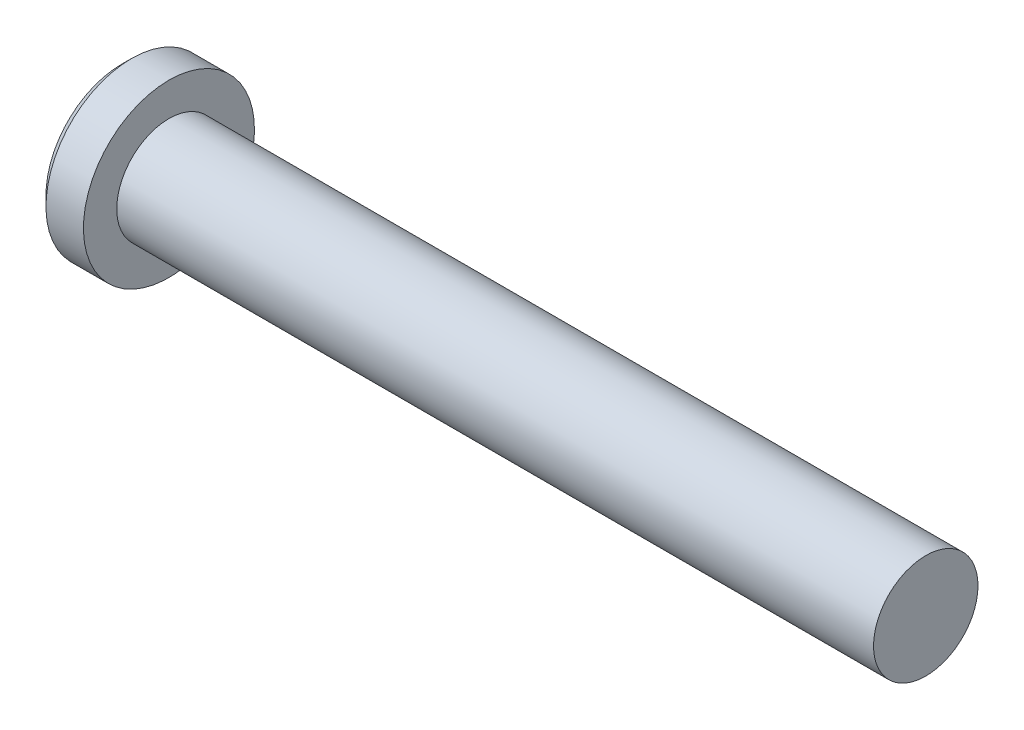
SolidWorks part; units mm, degrees
ref_plane "Front Plane" through (0, 0, 0) normal (0, 0, 1) x (1, 0, 0)
ref_plane "Top Plane" through (0, 0, 0) normal (0, 1, 0) x (1, 0, 0)
ref_plane "Right Plane" through (0, 0, 0) normal (1, 0, 0) x (0, 0, -1)
sketch "Sketch1" plane through (0, 0, 0) normal (0, 0, 1) x (1, 0, 0)
  line L0 (12.7, 0) -> (-12.7, 0) construction
  line L1 (12.7, 1.7526) -> (12.7, -1.7526) construction
  line L2 (-12.7, 2.8702) -> (-12.7, -2.8702) construction
  line L3 (-12.7, 2.8702) -> (-13.9573, 2.8702) construction
  line L4 (-13.9573, 2.8702) -> (-14.2875, 2.54) construction
  line L5 (-14.2875, 2.54) -> (-14.2875, -2.54) construction
  line L6 (-14.2875, -2.54) -> (-13.9573, -2.8702) construction
  line L7 (-13.9573, -2.8702) -> (-12.7, -2.8702) construction
  point P7 (-13.0175, 0)
  point P12 (9.525, -1.7526)
  dimension "D1" = 45
  dimension "Dec." = 3.5052
  dimension "Length" = 25.4
  dimension "Head Dia" = 5.7404
  dimension "Head Height" = 1.5875
  dimension "Hex Depth" = 1.27
  dimension "Chamfer" = 0.3302
  dimension "D2" = 3.175
ref_plane "Plane1" through (12.7, 0, 0) normal (1, 0, 0) x (0, 0, -1)
ref_plane "Plane2" through (-14.2875, 0, 0) normal (1, 0, 0) x (0, 0, -1)
sketch "Sketch2" plane through (12.7, 0, 0) normal (1, 0, 0) x (0, 0, -1)
  circle A0 centre (0, 0) radius 1.7526
extrude "Boss-Extrude1" add sketch "Sketch2" against normal up to vertex (25.4 mm away) up to point (-12.7, 0, 0)
sketch "Sketch3" plane through (12.7, 0, 0) normal (1, 0, 0) x (0, 0, -1)
  circle A0 centre (0, 0) radius 1.7526 construction
  circle A1 centre (0, 0) radius 1.7526
curve "Helix/Spiral1" pitch 0.7937 height 26.1937 turns 33 parameters "Pitch"=0.7937
chamfer "Chamfer1" [suppressed] distance 0.5953 angle 45
sketch "Sketch5" plane through (0, 0, 0) normal (0, 0, 1) x (1, 0, 0)
  line L0 (12.3527, 1.7526) -> (13.0473, 1.7526)
  line L1 (13.0473, 1.7526) -> (12.7496, 1.237)
  line L2 (12.7496, 1.237) -> (12.6504, 1.237)
  line L3 (12.6504, 1.237) -> (12.3527, 1.7526)
  line L4 (12.7, 1.237) -> (12.7, 1.7526) construction
  line L5 (12.5016, 1.4948) -> (12.8984, 1.4948) construction
  dimension "D1" = 60
  dimension "D2" = 0.3969
  dimension "D3" = 0.0992
sweep "Cut-Sweep1" [suppressed] cut profiles "Sketch5" path "Helix/Spiral1"
sketch "Sketch4" plane through (-14.2875, 0, 0) normal (1, 0, 0) x (0, 0, -1)
  line L0 (-2.8702, 0.7937) -> (2.8702, 0.7937) construction
  line L1 (0, 0.9165) -> (-0.7937, 0.4583)
  line L2 (-0.7937, 0.4583) -> (-0.7937, -0.4583)
  line L3 (-0.7937, -0.4583) -> (0, -0.9165)
  line L4 (0, -0.9165) -> (0.7937, -0.4583)
  line L5 (0.7937, -0.4583) -> (0.7937, 0.4583)
  line L6 (0.7937, 0.4583) -> (0, 0.9165)
  line L7 (0, 0) -> (0, 0.7937) construction
  circle A0 centre (0, 0) radius 0.7937 construction
  dimension "Hex Size" = 1.5875
  dimension "D1" = 5.7404
  dimension "D2" = 0.7937
sketch "Sketch6" plane through (0, 0, 0) normal (0, 0, 1) x (1, 0, 0)
  line L0 (-13.9573, 2.8702) -> (-14.2875, 2.54) construction
  line L1 (-12.7, 2.8702) -> (-13.9573, 2.8702) construction
  line L2 (-12.7, 2.8702) -> (-12.7, -2.8702) construction
  line L3 (-14.2875, 2.54) -> (-14.2875, -2.54) construction
  line L4 (-13.9573, 2.8702) -> (-14.2875, 2.54)
  line L5 (-12.7, 2.8702) -> (-13.9573, 2.8702)
  line L6 (-12.7, 2.8702) -> (-12.7, 0)
  line L7 (-14.2875, 2.54) -> (-14.2875, 0)
  line L8 (-12.7, 0) -> (-14.2875, 0) construction
  line L9 (-12.7, 0) -> (-14.2875, 0)
revolve "Revolve1" add sketch "Sketch6" angle 360 about L8
extrude "Cut-Extrude1" [suppressed] cut sketch "Sketch4" along normal up to vertex
sketch "Sketch8" plane through (-14.2875, 0, 0) normal (-1, 0, 0) x (0, 0, 1)
  circle A1 centre (0, 0) radius 0.9165
extrude "Cut-Extrude2" [suppressed] cut sketch "Sketch8" against normal through all draft 45
equation "\"D3@Helix/Spiral1\" = \"Length@Sketch1\"+\"Pitch@Helix/Spiral1\""
equation "\"D3@Sketch5\" = \"Pitch@Helix/Spiral1\"*.125"
equation "\"D2@Sketch5\" = \"Pitch@Helix/Spiral1\"*.50"
equation "\"D1@Chamfer1\" = \"Pitch@Helix/Spiral1\"*.75"
equation "\"D2@Sketch1\" = \"Pitch@Helix/Spiral1\"*4"
equation "\"D1@Sketch4\" = \"Head Dia@Sketch1\""
